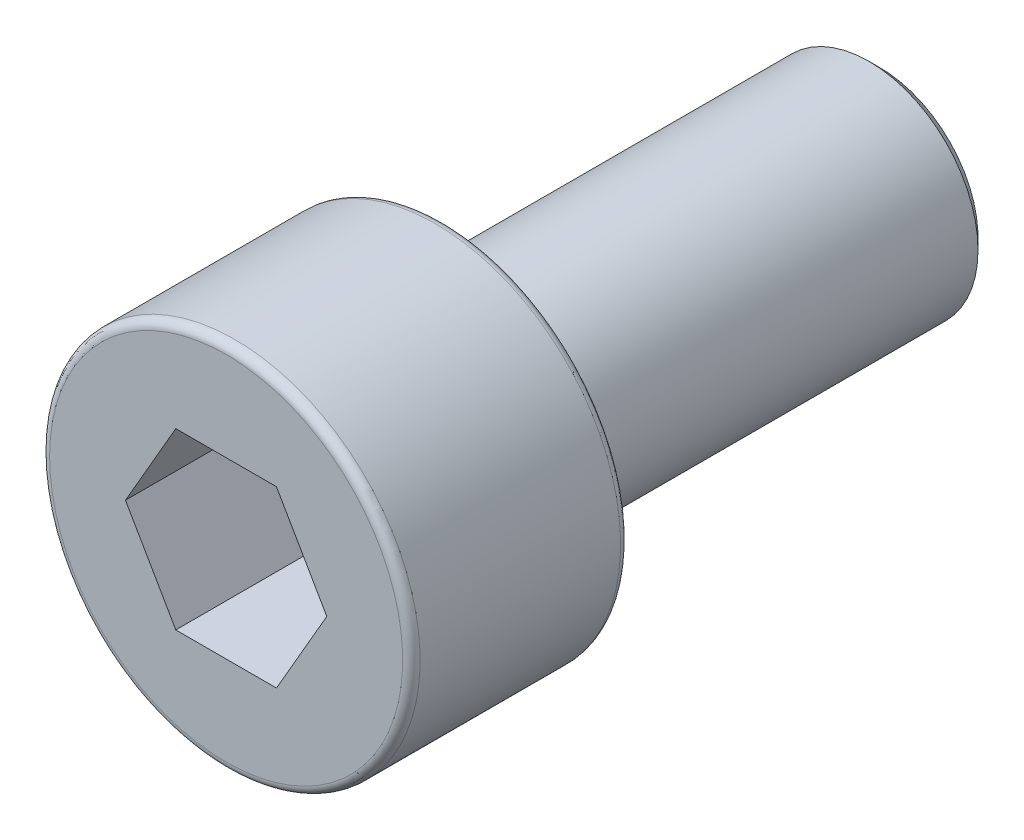
SolidWorks part; units mm, degrees
ref_plane "Front Plane" through (0, 0, 0) normal (0, 0, 1) x (1, 0, 0)
ref_plane "Top Plane" through (0, 0, 0) normal (0, 1, 0) x (1, 0, 0)
ref_plane "Right Plane" through (0, 0, 0) normal (1, 0, 0) x (0, 0, -1)
ref_plane "Plane1" through (0, 0, 15) normal (0, 0, 1) x (1, 0, 0)
sketch "Sketch1" plane through (0, 0, 15) normal (0, 0, 1) x (1, 0, 0)
  circle A0 centre (0, 0) radius 4.25
extrude "Boss-Extrude1" add sketch "Sketch1" against normal blind 5
sketch "Sketch2" plane through (0, 0, 10) normal (0, 0, -1) x (-1, 0, 0)
  circle A0 centre (0, 0) radius 2.5
extrude "Boss-Extrude2" add sketch "Sketch2" along normal blind 10
sketch "Sketch3" plane through (0, 0, 15) normal (0, 0, 1) x (1, 0, 0)
  line L0 (-2.3094, 0) -> (-1.1547, -2)
  line L1 (-1.1547, -2) -> (1.1547, -2)
  line L2 (1.1547, -2) -> (2.3094, 0)
  line L3 (2.3094, 0) -> (1.1547, 2)
  line L4 (1.1547, 2) -> (-1.1547, 2)
  line L5 (-1.1547, 2) -> (-2.3094, 0)
extrude "Cut-Extrude1" cut sketch "Sketch3" against normal blind 4
chamfer "Chamfer1" distance 0.25 angle 45 1 edges at (-2.5, 0, 0)
fillet "Fillet1" radius 0.2 2 edges at (-4.25, 0, 10) (-4.25, 0, 15) tangent propagation no
ref_axis "Axis1" through (0, 0, -2.1501) along (0, 0, 1)
